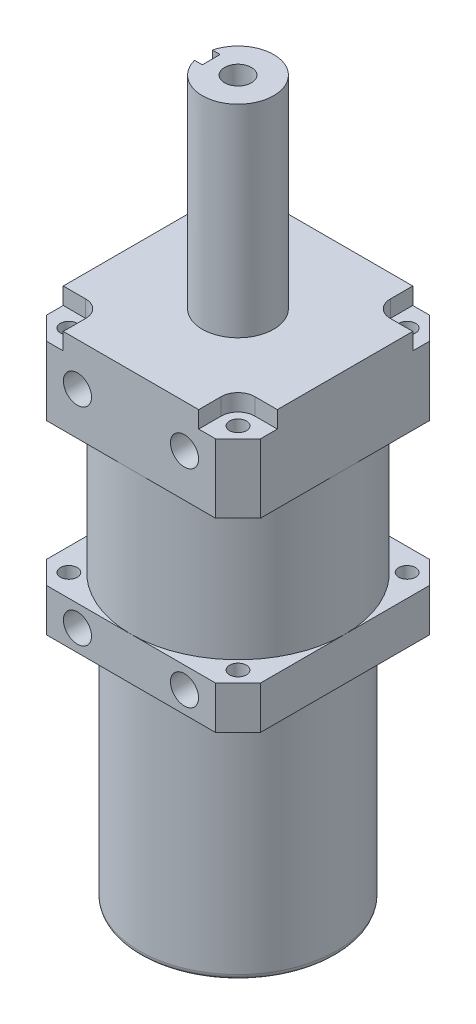
SolidWorks part; units mm, degrees
ref_plane "Alzado" through (0, 0, 0) normal (0, 0, 1) x (1, 0, 0)
ref_plane "Planta" through (0, 0, 0) normal (0, 1, 0) x (1, 0, 0)
ref_plane "Vista lateral" through (0, 0, 0) normal (1, 0, 0) x (0, 0, -1)
sketch "Croquis1" plane through (0, 0, 0) normal (0, 1, 0) x (1, 0, 0)
  line L0 (-15.05, 19.05) -> (-19.05, 15.05)
  line L1 (15.05, -19.05) -> (-15.05, -19.05)
  line L2 (19.05, -15.05) -> (19.05, 15.05)
  line L3 (15.05, 19.05) -> (-15.05, 19.05)
  line L4 (-19.05, -15.05) -> (-19.05, 15.05)
  line L5 (19.05, -19.05) -> (-19.05, 19.05) construction
  line L6 (19.05, 19.05) -> (-19.05, -19.05) construction
  line L7 (-15.05, -19.05) -> (-19.05, -15.05)
  line L8 (19.05, -15.05) -> (15.05, -19.05)
  line L9 (19.05, 15.05) -> (15.05, 19.05)
  line L10 (-19.05, 15.05) -> (-19.05, 19.05) construction
  line L11 (-19.05, 19.05) -> (-15.05, 19.05) construction
  line L12 (15.05, 19.05) -> (19.05, 19.05) construction
  line L13 (19.05, 19.05) -> (19.05, 15.05) construction
  line L14 (19.05, -15.05) -> (19.05, -19.05) construction
  line L15 (19.05, -19.05) -> (15.05, -19.05) construction
  line L16 (-15.05, -19.05) -> (-19.05, -19.05) construction
  line L17 (-19.05, -19.05) -> (-19.05, -15.05) construction
  point P0 (0, 0)
  dimension "D1" = 38.1
extrude "Saliente-Extruir1" add sketch "Croquis1" along normal blind 15.24
sketch "Croquis2" plane through (0, 15.24, 0) normal (0, 1, 0) x (1, 0, 0)
  circle A0 centre (0, 0) radius 6.35
  dimension "D1" = 12.7
extrude "Saliente-Extruir2" add sketch "Croquis2" along normal blind 36
ref_plane "Plano1" through (-6.35, 0, 0) normal (-1, 0, 0) x (0, 0, 1)
sketch "Croquis3" plane through (-6.35, 0, 0) normal (-1, 0, 0) x (0, 0, 1)
  line L0 (-1.5875, 51.24) -> (-1.5875, 19.49)
  line L1 (6.35, 51.24) -> (-6.35, 51.24) construction
  line L2 (-1.5875, 51.24) -> (1.5825, 51.24)
  line L3 (1.5825, 51.24) -> (1.5825, 19.49)
  line L4 (-6.35, 51.24) -> (-6.35, 15.24) construction
  arc A0 (-1.5875, 19.49) -> (1.5825, 19.49) centre (-0.0025, 19.49) ccw
  dimension "D1" = 3.17
  dimension "D2" = 31.75
  dimension "D3" = 4.7625
extrude "Cortar-Extruir1" cut sketch "Croquis3" against normal blind 1.585
sketch "Croquis4" plane through (0, 0, 0) normal (0, -1, 0) x (1, 0, 0)
  line L0 (-15.05, -15.05) -> (15.05, 15.05) construction
  line L1 (-15.05, 15.05) -> (15.05, -15.05) construction
  line L2 (15.05, -15.05) -> (15.05, 15.05) construction
  circle A0 centre (-15.05, -15.05) radius 1.5
  circle A1 centre (-15.05, 15.05) radius 1.5
  circle A2 centre (15.05, 15.05) radius 1.5
  circle A3 centre (15.05, -15.05) radius 1.5
  dimension "D1" = 3
  dimension "D2" = 90
  dimension "D3" = 30.1
extrude "Cortar-Extruir2" cut sketch "Croquis4" against normal through all
sketch "Croquis5" plane through (0, 0, 0) normal (0, -1, 0) x (1, 0, 0)
  line L0 (19.05, 15.05) -> (19.05, -15.05) construction
  circle A0 centre (0, 0) radius 19.05
extrude "Saliente-Extruir3" add sketch "Croquis5" along normal blind 25.4
sketch "Croquis6" plane through (0, -25.4, 0) normal (0, -1, 0) x (1, 0, 0)
  line L0 (-19.05, -15.05) -> (-15.05, -19.05)
  line L1 (-15.05, -19.05) -> (15.05, -19.05)
  line L2 (15.05, -19.05) -> (19.05, -15.05)
  line L3 (19.05, -15.05) -> (19.05, 15.05)
  line L4 (19.05, 15.05) -> (15.05, 19.05)
  line L5 (15.05, 19.05) -> (-15.05, 19.05)
  line L6 (-15.05, 19.05) -> (-19.05, 15.05)
  line L7 (-19.05, 15.05) -> (-19.05, -15.05)
  circle A0 centre (-15.05, 15.05) radius 1.5
  circle A1 centre (-15.05, -15.05) radius 1.5
  circle A2 centre (15.05, -15.05) radius 1.5
  circle A3 centre (15.05, 15.05) radius 1.5
  circle A4 centre (15.05, -15.05) radius 1.5 construction
extrude "Saliente-Extruir4" add sketch "Croquis6" along normal blind 7.62
sketch "Croquis7" plane through (0, 15.24, 0) normal (0, 1, 0) x (1, 0, 0)
  line L0 (-19.05, -12.05) -> (-12.05, -12.05)
  line L1 (-19.05, 15.05) -> (-19.05, -15.05) construction
  line L2 (-12.05, -12.05) -> (-12.05, -19.05)
  line L3 (-15.05, -19.05) -> (15.05, -19.05) construction
  line L4 (-12.05, -19.05) -> (-15.05, -19.05)
  line L5 (-15.05, -19.05) -> (-19.05, -15.05)
  line L6 (-19.05, -15.05) -> (-19.05, -12.05)
  line L7 (-19.05, 0) -> (19.05, 0) construction
  line L8 (0, -19.05) -> (0, 19.05) construction
  line L9 (-12.05, 19.05) -> (-12.05, 12.05)
  line L10 (-12.05, 12.05) -> (-19.05, 12.05)
  line L11 (-19.05, 12.05) -> (-19.05, 15.05)
  line L12 (-19.05, 15.05) -> (-15.05, 19.05)
  line L13 (-15.05, 19.05) -> (-12.05, 19.05)
  line L14 (19.05, 12.05) -> (12.05, 12.05)
  line L15 (12.05, 12.05) -> (12.05, 19.05)
  line L16 (12.05, 19.05) -> (15.05, 19.05)
  line L17 (15.05, 19.05) -> (19.05, 15.05)
  line L18 (19.05, 15.05) -> (19.05, 12.05)
  line L19 (12.05, -19.05) -> (12.05, -12.05)
  line L20 (12.05, -12.05) -> (19.05, -12.05)
  line L21 (19.05, -12.05) -> (19.05, -15.05)
  line L22 (19.05, -15.05) -> (15.05, -19.05)
  line L23 (15.05, -19.05) -> (12.05, -19.05)
  point P35 (0, 0)
  dimension "D2" = 7
  dimension "D3" = 7
  dimension "D1" = 4
extrude "Cortar-Extruir3" cut sketch "Croquis7" against normal blind 3
fillet "Redondeo1" radius 3 4 edges at (-12.05, 13.74, 12.05) (12.05, 13.74, 12.05) (12.05, 13.74, -12.05) (-12.05, 13.74, -12.05)
sketch "Croquis8" plane through (0, -33.02, 0) normal (0, -1, 0) x (1, 0, 0)
  circle A0 centre (0, 0) radius 17.5
  dimension "D1" = 35
extrude "Saliente-Extruir5" add sketch "Croquis8" along normal blind 43
fillet "Redondeo2" radius 1 1 edges at (0, -76.02, -17.5)
sketch "Croquis9" plane through (0, 0, 19.05) normal (0, 0, -1) x (-1, 0, 0)
  line L1 (-9.525, 7.62) -> (9.525, 7.62) construction
  line L2 (-9.525, 7.62) -> (-9.525, -29.21) construction
  line L3 (-9.525, -29.21) -> (9.525, -29.21) construction
  line L4 (9.525, 7.62) -> (9.525, -29.21) construction
  line L5 (0, 0) -> (0, 7.62) construction
  line L6 (-17.5, -33.02) -> (17.5, -33.02) construction
  line L7 (12.05, 15.24) -> (-12.05, 15.24) construction
  circle A0 centre (9.525, 7.62) radius 2.5
  circle A1 centre (-9.525, 7.62) radius 2.5
  circle A2 centre (-9.525, -29.21) radius 2.5
  circle A3 centre (9.525, -29.21) radius 2.5
  dimension "D1" = 5
  dimension "D2" = 7.62
  dimension "D3" = 9.525
  dimension "D4" = 3.81
extrude "Cortar-Extruir4" cut sketch "Croquis9" along normal blind 10
extrude "Cortar-Extruir5" cut sketch "Croquis9<2>" against normal blind 10 from surface starting at face at (0, 8.8267, -19.05)
sketch "Croquis9<2>" plane through (0, 0, 19.05) normal (0, 0, -1) x (-1, 0, 0) same geometry as "Croquis9"
sketch "Croquis10" plane through (0, 51.24, 0) normal (0, 1, 0) x (1, 0, 0)
  circle A0 centre (0, 0) radius 2.3841
  dimension "D1" = 4.7681
extrude "Cortar-Extruir6" cut sketch "Croquis10" against normal blind 15
